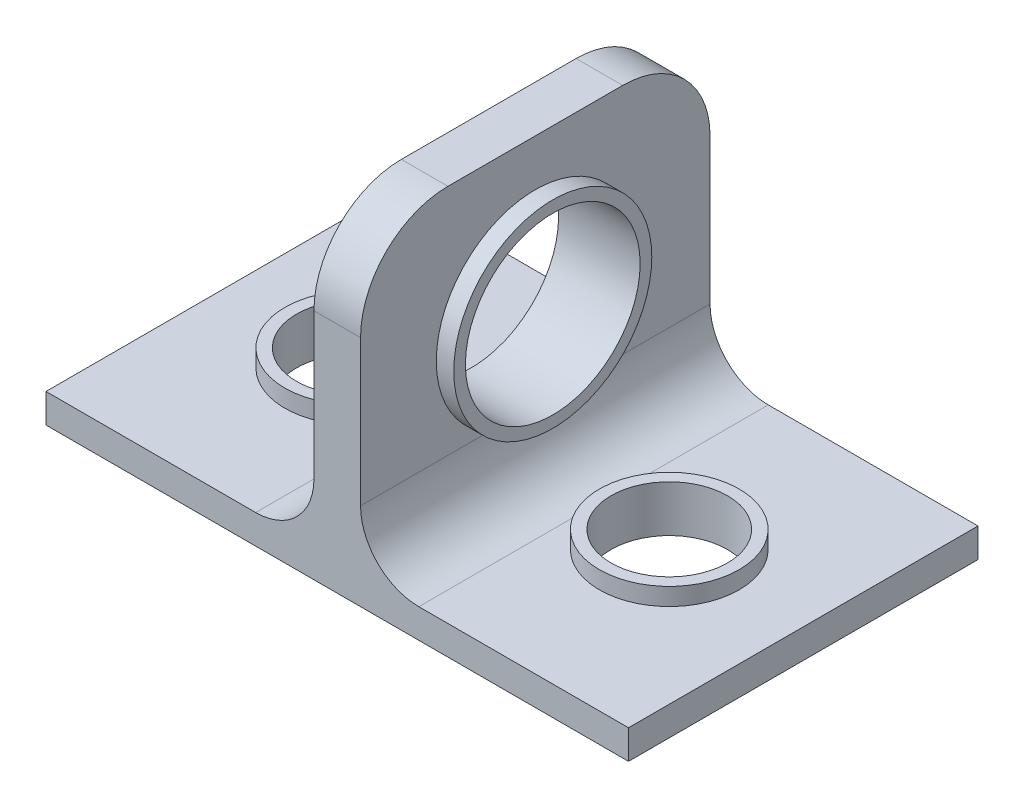
SolidWorks part; units mm, degrees
ref_plane "Front Plane" through (0, 0, 0) normal (0, 0, 1) x (1, 0, 0)
ref_plane "Top Plane" through (0, 0, 0) normal (0, 1, 0) x (1, 0, 0)
ref_plane "Right Plane" through (0, 0, 0) normal (1, 0, 0) x (0, 0, -1)
sketch "Sketch1" plane through (0, 0, 0) normal (0, 0, 1) x (1, 0, 0)
  line L0 (0, 0) -> (0, 5)
  line L1 (0, 5) -> (46, 5)
  line L2 (46, 5) -> (46, 55)
  line L3 (46, 55) -> (54, 55)
  line L4 (54, 55) -> (54, 5)
  line L5 (54, 5) -> (100, 5)
  line L6 (100, 5) -> (100, 0)
  line L7 (100, 0) -> (0, 0)
  point P3 (46, 30)
  dimension "D1" = 100
  dimension "D2" = 5
  dimension "D3" = 5
  dimension "D4" = 55
  dimension "D5" = 8
extrude "Boss-Extrude1" add sketch "Sketch1" along normal mid plane 60
fillet "Fillet1" radius 10 2 edges at (46, 5, 0) (54, 5, 0)
sketch "Sketch2" plane through (0, 0, 0) normal (0, 1, 0) x (1, 0, 0)
  line L0 (100, -30) -> (100, 30) construction
  line L1 (36, -30) -> (0, -30) construction
  circle A0 centre (23, 0) radius 10
  circle A1 centre (23, 0) radius 12
  circle A2 centre (77, 0) radius 10
  circle A3 centre (77, 0) radius 12
  point P6 (0, 0)
  point P9 (0, 0)
  point P10 (0, 0)
  dimension "D1" = 24
  dimension "D2" = 20
  dimension "D3" = 20
  dimension "D4" = 24
  dimension "D5" = 23
  dimension "D6" = 54
  dimension "D7" = 30
extrude "Cut-Extrude1" cut sketch "Sketch2" along normal up to next contours A0 | A0 | A2 region at (23, 0, 0)
extrude "Boss-Extrude2" add sketch "Sketch2<3>" along normal blind 8
sketch "Sketch2<3>" plane through (0, 0, 0) normal (0, 1, 0) x (1, 0, 0) same geometry as "Sketch2"
sketch "Sketch3" plane through (46, 0, 0) normal (-1, 0, 0) x (0, 0, 1)
  line L0 (30, 0) -> (-30, 0) construction
  line L1 (30, 55) -> (30, 15) construction
  circle A0 centre (0, 30) radius 15
  circle A1 centre (0, 30) radius 17
  dimension "D1" = 34
  dimension "D2" = 30
  dimension "D3" = 30
  dimension "D4" = 30
extrude "Cut-Extrude2" cut sketch "Sketch3" against normal up to next contours A0 region at (46, 30, 0)
extrude "Boss-Extrude3" add sketch "Sketch3<3>" along normal blind 3 and the other way blind 11
sketch "Sketch3<3>" plane through (46, 0, 0) normal (-1, 0, 0) x (0, 0, 1) same geometry as "Sketch3"
fillet "Fillet2" radius 15 2 edges at (50, 55, -30) (50, 55, 30)
